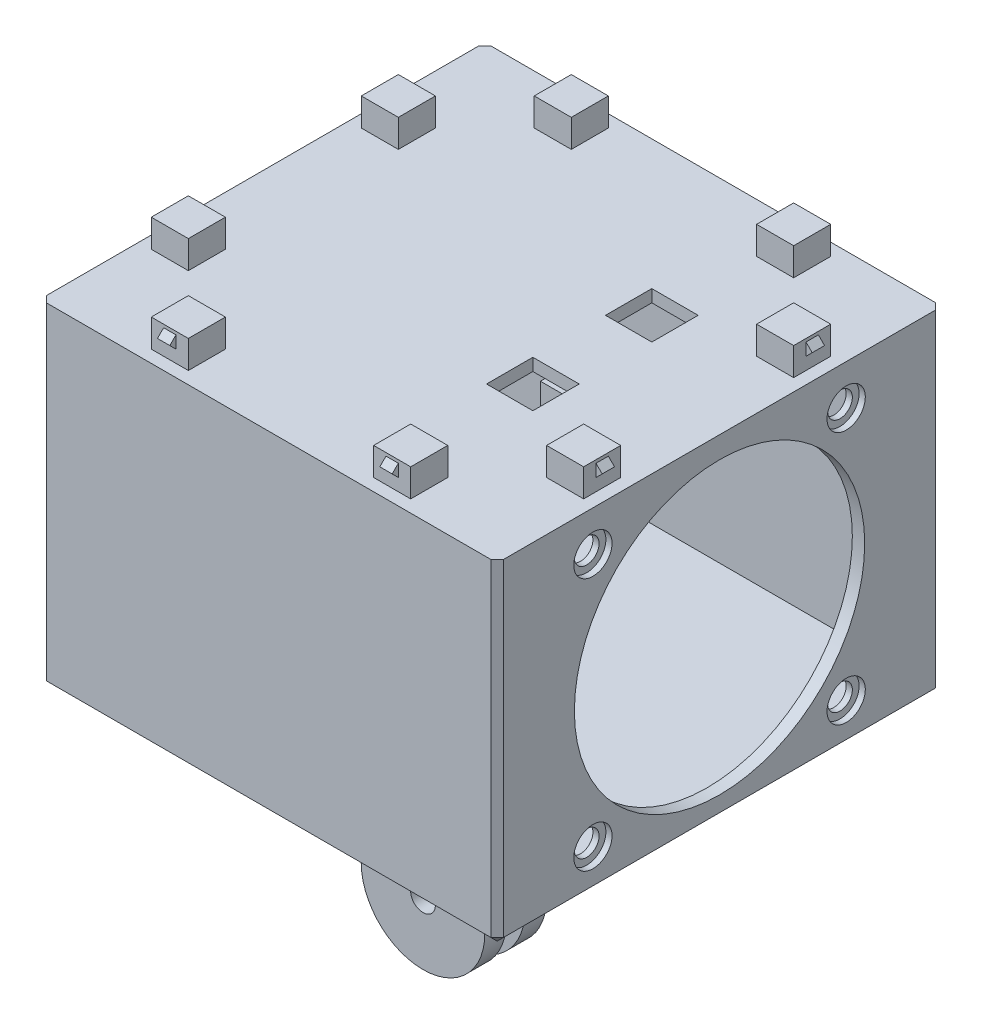
SolidWorks part; units mm, degrees
ref_plane "前视基准面" through (0, 0, 0) normal (0, 0, 1) x (1, 0, 0)
ref_plane "上视基准面" through (0, 0, 0) normal (0, 1, 0) x (1, 0, 0)
ref_plane "右视基准面" through (0, 0, 0) normal (1, 0, 0) x (0, 0, -1)
sketch "草图1" plane through (0, 0, 0) normal (0, 1, 0) x (1, 0, 0)
  line L1 (-65.7153, 32.1762) -> (8.2847, 32.1762)
  line L2 (-65.7153, 32.1762) -> (-65.7153, -39.8238)
  line L3 (-65.7153, -39.8238) -> (8.2847, -39.8238)
  line L4 (8.2847, 32.1762) -> (8.2847, -39.8238)
  dimension "D1" = 74
  dimension "D5" = 72
extrude "凸台-拉伸1" add sketch "草图1" along normal blind 54
sketch "草图2" plane through (0, 54, 0) normal (0, 1, 0) x (1, 0, 0)
  line L0 (8.2847, -39.8238) -> (8.2847, 32.1762) construction
  line L1 (6.2847, 30.1762) -> (-63.7153, 30.1762)
  line L2 (6.2847, 30.1762) -> (6.2847, -37.8238)
  line L3 (6.2847, -37.8238) -> (-63.7153, -37.8238)
  line L4 (-63.7153, 30.1762) -> (-63.7153, -37.8238)
  line L5 (-65.7153, -39.8238) -> (8.2847, -39.8238) construction
  line L6 (8.2847, 32.1762) -> (-65.7153, 32.1762) construction
  line L7 (-65.7153, 32.1762) -> (-65.7153, -39.8238) construction
  dimension "D1" = 2
  dimension "D2" = 2
  dimension "D3" = 2
  dimension "D4" = 2
extrude "切除-拉伸1" cut sketch "草图2" against normal blind 52
sketch "草图4" plane through (8.2847, 0, 0) normal (1, 0, 0) x (0, 0, -1)
  line L1 (32.1762, 54) -> (32.1762, 0) construction
  line L2 (-39.8238, 0) -> (32.1762, 0) construction
  circle A0 centre (-3.8238, 27) radius 23.5
  circle A1 centre (16.6762, 6.5) radius 2
  circle A2 centre (-24.3238, 47.5) radius 2
  circle A3 centre (-24.3238, 6.5) radius 2
  circle A4 centre (16.6762, 47.5) radius 2
  dimension "D1" = 47
  dimension "D2" = 20.5
  dimension "D8" = 4
  dimension "D3" = 20.5
  dimension "D4" = 20.5
  dimension "D5" = 20.5
  dimension "D6" = 36
  dimension "D7" = 27
extrude "切除-拉伸2" cut sketch "草图4" against normal blind 2
sketch "草图5" plane through (0, 0, 0) normal (0, -1, 0) x (1, 0, 0)
  line L0 (-65.7153, -32.1762) -> (-65.7153, 39.8238) construction
  line L1 (-63.7153, 37.8238) -> (-49.7153, 37.8238)
  line L2 (-63.7153, 37.8238) -> (-63.7153, -30.1762)
  line L3 (-63.7153, -30.1762) -> (-49.7153, -30.1762)
  line L4 (-49.7153, 37.8238) -> (-49.7153, -30.1762)
  line L5 (-65.7153, 39.8238) -> (8.2847, 39.8238) construction
  line L6 (8.2847, -32.1762) -> (-65.7153, -32.1762) construction
  dimension "D1" = 2
  dimension "D2" = 2
  dimension "D3" = 2
  dimension "D4" = 14
extrude "切除-拉伸3" cut sketch "草图5" against normal blind 2
sketch "草图6" plane through (0, 0, 37.8238) normal (0, 0, -1) x (-1, 0, 0)
  line L0 (63.7153, 54) -> (-6.2847, 54) construction
  line L1 (63.7153, 52) -> (54.7153, 52)
  line L2 (63.7153, 52) -> (63.7153, 54)
  line L3 (63.7153, 54) -> (54.7153, 54)
  line L4 (54.7153, 52) -> (54.7153, 54)
  line L9 (63.7153, 0) -> (63.7153, 54) construction
  dimension "D1" = 9
  dimension "D2" = 2
  dimension "D3" = 0
  dimension "D4" = 0
sketch "草图7" plane through (0, 0, -30.1762) normal (0, 0, 1) x (1, 0, 0)
  line L0 (-54.7153, 52) -> (-54.7153, 54) construction
  line L1 (-63.7153, 54) -> (-54.7153, 54)
  line L2 (-63.7153, 54) -> (-63.7153, 52)
  line L3 (-63.7153, 52) -> (-54.7153, 52)
  line L4 (-54.7153, 54) -> (-54.7153, 52)
  line L5 (-63.7153, 54) -> (-54.7153, 54) construction
  line L6 (6.2847, 54) -> (-63.7153, 54) construction
  line L7 (-63.7153, 0) -> (-63.7153, 54) construction
  point P12 (-63.7153, 53)
  dimension "D1" = 0
extrude "凸台-拉伸2" add sketch "草图6" along normal blind 5
extrude "凸台-拉伸3" add sketch "草图7" along normal blind 5
sketch "草图9" plane through (-65.7153, 0, 0) normal (-1, 0, 0) x (0, 0, 1)
  line L0 (39.8238, 54) -> (39.8238, 0) construction
  line L1 (35.8238, 50) -> (-28.1762, 50)
  line L2 (35.8238, 50) -> (35.8238, 4)
  line L3 (35.8238, 4) -> (-28.1762, 4)
  line L4 (-28.1762, 50) -> (-28.1762, 4)
  line L5 (-32.1762, 0) -> (39.8238, 0) construction
  line L6 (-32.1762, 54) -> (39.8238, 54) construction
  line L7 (-32.1762, 54) -> (-32.1762, 0) construction
  dimension "D1" = 4
  dimension "D2" = 4
  dimension "D3" = 4
  dimension "D4" = 4
extrude "切除-拉伸4" cut sketch "草图9" against normal up to next
sketch "草图10" plane through (0, 0, 37.8238) normal (0, 0, -1) x (-1, 0, 0)
  line L0 (49.7153, 2) -> (-6.2847, 2) construction
  line L9 (49.7153, 10) -> (45.7153, 10)
  line L10 (49.7153, 10) -> (49.7153, 18)
  line L11 (49.7153, 18) -> (45.7153, 18)
  line L12 (45.7153, 10) -> (45.7153, 18)
  line L13 (49.7153, 25) -> (49.7153, 33)
  line L14 (49.7153, 25) -> (45.7153, 25)
  line L15 (45.7153, 25) -> (45.7153, 33)
  line L16 (49.7153, 33) -> (45.7153, 33)
  line L17 (49.7153, 40) -> (49.7153, 48)
  line L18 (49.7153, 40) -> (45.7153, 40)
  line L19 (45.7153, 40) -> (45.7153, 48)
  line L20 (49.7153, 48) -> (45.7153, 48)
  line L21 (49.7153, 2) -> (49.7153, 0) construction
  point P0 (47.7153, 10)
  dimension "D1" = 4
  dimension "D2" = 8
  dimension "D3" = 8
  dimension "D4" = 3
extrude "凸台-拉伸5" add sketch "草图10" along normal blind 5
sketch "草图11" plane through (0, 0, -30.1762) normal (0, 0, 1) x (1, 0, 0)
  line L0 (6.2847, 2) -> (-49.7153, 2) construction
  line L1 (-45.7153, 10) -> (-49.7153, 10)
  line L2 (-45.7153, 10) -> (-45.7153, 18)
  line L3 (-45.7153, 18) -> (-49.7153, 18)
  line L4 (-49.7153, 10) -> (-49.7153, 18)
  line L5 (-45.7153, 25) -> (-45.7153, 33)
  line L6 (-45.7153, 25) -> (-49.7153, 25)
  line L7 (-49.7153, 25) -> (-49.7153, 33)
  line L8 (-45.7153, 33) -> (-49.7153, 33)
  line L9 (-45.7153, 40) -> (-45.7153, 48)
  line L10 (-45.7153, 40) -> (-49.7153, 40)
  line L11 (-49.7153, 40) -> (-49.7153, 48)
  line L12 (-45.7153, 48) -> (-49.7153, 48)
  line L13 (-49.7153, 2) -> (-49.7153, 0) construction
  dimension "D1" = 4
  dimension "D2" = 8
  dimension "D3" = 8
  dimension "D4" = 3
extrude "凸台-拉伸6" add sketch "草图11" along normal blind 5
sketch "草图15" plane through (0, 54, 0) normal (0, 1, 0) x (1, 0, 0)
  line L0 (6.2847, -37.8238) -> (6.2847, 30.1762) construction
  line L1 (-63.7153, 30.1762) -> (6.2847, 30.1762)
  line L2 (-63.7153, 30.1762) -> (-63.7153, -37.8238)
  line L3 (-63.7153, -37.8238) -> (6.2847, -37.8238)
  line L4 (6.2847, 30.1762) -> (6.2847, -37.8238)
  line L5 (-63.7153, 25.1762) -> (-63.7153, -32.8238) construction
extrude "凸台-拉伸7" add sketch "草图15" against normal blind 2
sketch "草图16" plane through (0, 54, 0) normal (0, 1, 0) x (1, 0, 0)
  line L0 (-43.7153, -31.8238) -> (-49.7153, -31.8238)
  line L1 (-57.7153, 16.1762) -> (-63.7153, 16.1762)
  line L2 (-57.7153, 16.1762) -> (-57.7153, 10.1762)
  line L3 (-57.7153, 10.1762) -> (-63.7153, 10.1762)
  line L4 (-63.7153, 16.1762) -> (-63.7153, 10.1762)
  line L5 (-43.7153, -31.8238) -> (-43.7153, -37.8238)
  line L6 (-43.7153, -37.8238) -> (-49.7153, -37.8238)
  line L7 (-49.7153, -31.8238) -> (-49.7153, -37.8238)
  line L8 (-7.7153, -31.8238) -> (-13.7153, -31.8238)
  line L9 (-7.7153, -31.8238) -> (-7.7153, -37.8238)
  line L10 (-7.7153, -37.8238) -> (-13.7153, -37.8238)
  line L11 (-13.7153, -31.8238) -> (-13.7153, -37.8238)
  line L12 (-43.7153, 30.1762) -> (-49.7153, 30.1762)
  line L13 (-43.7153, 30.1762) -> (-43.7153, 24.1762)
  line L14 (-43.7153, 24.1762) -> (-49.7153, 24.1762)
  line L15 (-49.7153, 30.1762) -> (-49.7153, 24.1762)
  line L16 (-7.7153, 30.1762) -> (-13.7153, 30.1762)
  line L17 (-7.7153, 30.1762) -> (-7.7153, 24.1762)
  line L18 (-7.7153, 24.1762) -> (-13.7153, 24.1762)
  line L19 (-13.7153, 30.1762) -> (-13.7153, 24.1762)
  line L20 (6.2847, 16.1762) -> (0.2847, 16.1762)
  line L21 (6.2847, 16.1762) -> (6.2847, 10.1762)
  line L22 (6.2847, 10.1762) -> (0.2847, 10.1762)
  line L23 (0.2847, 16.1762) -> (0.2847, 10.1762)
  line L24 (6.2847, -17.8238) -> (0.2847, -17.8238)
  line L25 (6.2847, -17.8238) -> (6.2847, -23.8238)
  line L26 (6.2847, -23.8238) -> (0.2847, -23.8238)
  line L27 (0.2847, -17.8238) -> (0.2847, -23.8238)
  line L32 (-57.7153, -17.8238) -> (-63.7153, -17.8238)
  line L33 (-57.7153, -17.8238) -> (-57.7153, -23.8238)
  line L34 (-57.7153, -23.8238) -> (-63.7153, -23.8238)
  line L35 (-63.7153, -17.8238) -> (-63.7153, -23.8238)
  line L36 (8.2847, 32.1762) -> (-65.7153, 32.1762) construction
  line L37 (-65.7153, -39.8238) -> (8.2847, -39.8238) construction
  line L38 (-65.7153, 32.1762) -> (-65.7153, -39.8238) construction
  line L39 (8.2847, -39.8238) -> (8.2847, 32.1762) construction
  point P42 (-10.7153, 30.1762)
  dimension "D1" = 16
  dimension "D2" = 16
  dimension "D3" = 16
  dimension "D4" = 16
  dimension "D5" = 16
  dimension "D6" = 16
  dimension "D7" = 16
  dimension "D8" = 16
  dimension "D9" = 6
  dimension "D10" = 2
  dimension "D11" = 2
  dimension "D12" = 2
  dimension "D13" = 2
extrude "凸台-拉伸8" add sketch "草图16" along normal blind 4.5
sketch "草图17" plane through (-63.7153, 0, 0) normal (-1, 0, 0) x (0, 0, 1)
  line L1 (-14.1762, 58) -> (-12.1762, 58)
  line L2 (-14.1762, 58) -> (-14.1762, 56)
  line L3 (-14.1762, 56) -> (-12.1762, 56)
  line L4 (-12.1762, 58) -> (-12.1762, 56)
  line L5 (19.8238, 58) -> (21.8238, 58)
  line L6 (19.8238, 58) -> (19.8238, 56)
  line L7 (19.8238, 56) -> (21.8238, 56)
  line L8 (21.8238, 58) -> (21.8238, 56)
  line L9 (17.8238, 54) -> (23.8238, 54) construction
  line L10 (23.8238, 58.5) -> (23.8238, 54) construction
  line L11 (-10.1762, 58.5) -> (-10.1762, 54) construction
  dimension "D1" = 2
  dimension "D2" = 2
  dimension "D3" = 2
  dimension "D4" = 2
extrude "凸台-拉伸9" add sketch "草图17" along normal blind 1
sketch "草图18" plane through (0, 0, 37.8238) normal (0, 0, 1) x (1, 0, 0)
  line L0 (-13.7153, 54) -> (-7.7153, 54) construction
  line L1 (-9.7153, 56) -> (-11.7153, 56)
  line L2 (-9.7153, 56) -> (-9.7153, 58)
  line L3 (-9.7153, 58) -> (-11.7153, 58)
  line L4 (-11.7153, 56) -> (-11.7153, 58)
  line L5 (-45.7153, 56) -> (-47.7153, 56)
  line L6 (-45.7153, 56) -> (-45.7153, 58)
  line L7 (-45.7153, 58) -> (-47.7153, 58)
  line L8 (-47.7153, 56) -> (-47.7153, 58)
  line L9 (-7.7153, 58.5) -> (-7.7153, 54) construction
  line L10 (-43.7153, 58.5) -> (-43.7153, 54) construction
  point P11 (-9.7153, 57)
  dimension "D1" = 2
  dimension "D2" = 2
  dimension "D3" = 2
  dimension "D4" = 2
extrude "凸台-拉伸10" add sketch "草图18" along normal blind 1
sketch "草图19" plane through (6.2847, 0, 0) normal (1, 0, 0) x (0, 0, -1)
  line L0 (10.1762, 54) -> (16.1762, 54) construction
  line L1 (14.1762, 56) -> (12.1762, 56)
  line L2 (14.1762, 56) -> (14.1762, 58)
  line L3 (14.1762, 58) -> (12.1762, 58)
  line L4 (12.1762, 56) -> (12.1762, 58)
  line L5 (-19.8238, 56) -> (-21.8238, 56)
  line L6 (-19.8238, 56) -> (-19.8238, 58)
  line L7 (-19.8238, 58) -> (-21.8238, 58)
  line L8 (-21.8238, 56) -> (-21.8238, 58)
  line L9 (16.1762, 58.5) -> (16.1762, 54) construction
  line L10 (-17.8238, 58.5) -> (-17.8238, 54) construction
  dimension "D1" = 2
  dimension "D2" = 2
  dimension "D3" = 2
  dimension "D4" = 2
extrude "凸台-拉伸11" add sketch "草图19" along normal blind 1
sketch "草图20" plane through (0, 0, -30.1762) normal (0, 0, -1) x (-1, 0, 0)
  line L1 (47.7153, 56) -> (45.7153, 56)
  line L2 (47.7153, 56) -> (47.7153, 58)
  line L3 (47.7153, 58) -> (45.7153, 58)
  line L4 (45.7153, 56) -> (45.7153, 58)
  line L5 (11.7153, 56) -> (9.7153, 56)
  line L6 (11.7153, 56) -> (11.7153, 58)
  line L7 (11.7153, 58) -> (9.7153, 58)
  line L8 (9.7153, 56) -> (9.7153, 58)
  line L9 (43.7153, 54) -> (49.7153, 54) construction
  line L10 (49.7153, 58.5) -> (49.7153, 54) construction
  line L11 (13.7153, 58.5) -> (13.7153, 54) construction
  dimension "D1" = 2
  dimension "D2" = 2
  dimension "D3" = 2
  dimension "D4" = 2
extrude "凸台-拉伸12" add sketch "草图20" along normal blind 1
sketch "草图21" plane through (0, 52, 0) normal (0, -1, 0) x (-1, 0, 0)
  line L1 (10.1869, -15.5749) -> (17.6869, -15.5749)
  line L2 (10.1869, -15.5749) -> (10.1869, -8.0749)
  line L3 (10.1869, -8.0749) -> (17.6869, -8.0749)
  line L4 (17.6869, -15.5749) -> (17.6869, -8.0749)
  line L5 (10.1869, 3.6832) -> (17.6869, 3.6832)
  line L6 (10.1869, 3.6832) -> (10.1869, 11.1832)
  line L7 (10.1869, 11.1832) -> (17.6869, 11.1832)
  line L8 (17.6869, 3.6832) -> (17.6869, 11.1832)
  dimension "D1" = 7.5
extrude "切除-拉伸5" cut sketch "草图21" against normal up to next
sketch "草图25" plane through (0, 0, 0) normal (0, -1, 0) x (1, 0, 0)
  line L0 (8.2847, 39.8238) -> (8.2847, -32.1762) construction
  line L1 (-24.7278, 8.8238) -> (-44.7278, 8.8238)
  line L2 (-24.7278, 8.8238) -> (-24.7278, -1.1762)
  line L3 (-24.7278, -1.1762) -> (-44.7278, -1.1762)
  line L4 (-44.7278, 8.8238) -> (-44.7278, -1.1762)
  point P6 (8.2847, 3.8238)
  point P7 (-24.7278, 3.8238)
  dimension "D1" = 20
  dimension "D2" = 10
extrude "凸台-拉伸15" add sketch "草图25" along normal blind 30
sketch "草图26" plane through (0, 0, 8.8238) normal (0, 0, 1) x (1, 0, 0)
  line L0 (-24.7278, -30) -> (-44.7278, -30) construction
  circle A0 centre (-34.7278, -30) radius 10
extrude "凸台-拉伸16" add sketch "草图26" against normal blind 10
sketch "草图27" plane through (0, 0, 8.8238) normal (0, 0, 1) x (1, 0, 0)
  circle A0 centre (-34.7278, -30) radius 2
  arc A1 (-44.7278, -30) -> (-24.7278, -30) centre (-34.7278, -30) ccw construction
  dimension "D1" = 4
extrude "切除-拉伸6" cut sketch "草图27" against normal blind 10
sketch "草图29" plane through (-44.7278, 0, 0) normal (-1, 0, 0) x (0, 0, 1)
  line L1 (5.3238, -40) -> (2.3238, -40)
  line L2 (5.3238, -40) -> (5.3238, -13)
  line L3 (5.3238, -13) -> (2.3238, -13)
  line L4 (2.3238, -40) -> (2.3238, -13)
  line L5 (8.8238, 0) -> (-1.1762, 0) construction
  point P7 (3.8238, 0)
  point P8 (3.8238, -13)
  dimension "D1" = 3
  dimension "D2" = 27
extrude "切除-拉伸7" cut sketch "草图29" against normal up to next
sketch "草图30" plane through (0, -13, 0) normal (0, -1, 0) x (1, 0, 0)
  line L0 (-24.7278, 5.3238) -> (-44.7278, 5.3238) construction
  line L1 (-33.2278, 2.3238) -> (-36.2278, 2.3238)
  line L2 (-33.2278, 2.3238) -> (-33.2278, 5.3238)
  line L3 (-33.2278, 5.3238) -> (-36.2278, 5.3238)
  line L4 (-36.2278, 2.3238) -> (-36.2278, 5.3238)
  line L5 (-24.7278, 2.3238) -> (-44.7278, 2.3238) construction
  point P8 (-34.7278, 2.3238)
  point P9 (-34.7278, 2.3238)
  dimension "D1" = 3
extrude "切除-拉伸8" cut sketch "草图30" against normal up to next
chamfer "倒角1" distance 1 angle 45 8 edges at (-65.7153, 27, 39.8238) (8.2847, 27, 39.8238) (8.2847, 27, -32.1762) (-65.7153, 27, -32.1762) (-28.7153, 0, 39.8238) (-65.7153, 0, 3.8238) (-28.7153, 0, -32.1762) (8.2847, 0, 3.8238)
chamfer "倒角2" distance 1 angle 45 8 edges at (7.2847, 58, 20.8238) (7.2847, 58, -13.1762) (-10.7153, 58, -31.1762) (-46.7153, 58, -31.1762) (-64.7153, 58, -13.1762) (-64.7153, 58, 20.8238) (-10.7153, 58, 38.8238) (-46.7153, 58, 38.8238)
sketch "草图31" plane through (8.2847, 0, 0) normal (1, 0, 0) x (0, 0, -1)
  circle A0 centre (16.6762, 6.5) radius 3.1
  circle A1 centre (-24.3238, 6.5) radius 3.1
  circle A2 centre (-24.3238, 47.5) radius 3.1
  circle A3 centre (16.6762, 47.5) radius 3.1
  circle A4 centre (16.6762, 6.5) radius 2 construction
  circle A5 centre (-24.3238, 6.5) radius 2 construction
  circle A6 centre (-24.3238, 47.5) radius 2 construction
  circle A7 centre (16.6762, 47.5) radius 2 construction
  dimension "D1" = 6.2
extrude "切除-拉伸9" cut sketch "草图31" against normal blind 1
chamfer "倒角3" distance 1 angle 45 8 edges at (-64.7153, 56, 20.8238) (-64.7153, 56, -13.1762) (-46.7153, 56, -31.1762) (-10.7153, 56, -31.1762) (7.2847, 56, -13.1762) (7.2847, 56, 20.8238) (-46.7153, 56, 38.8238) (-10.7153, 56, 38.8238)
